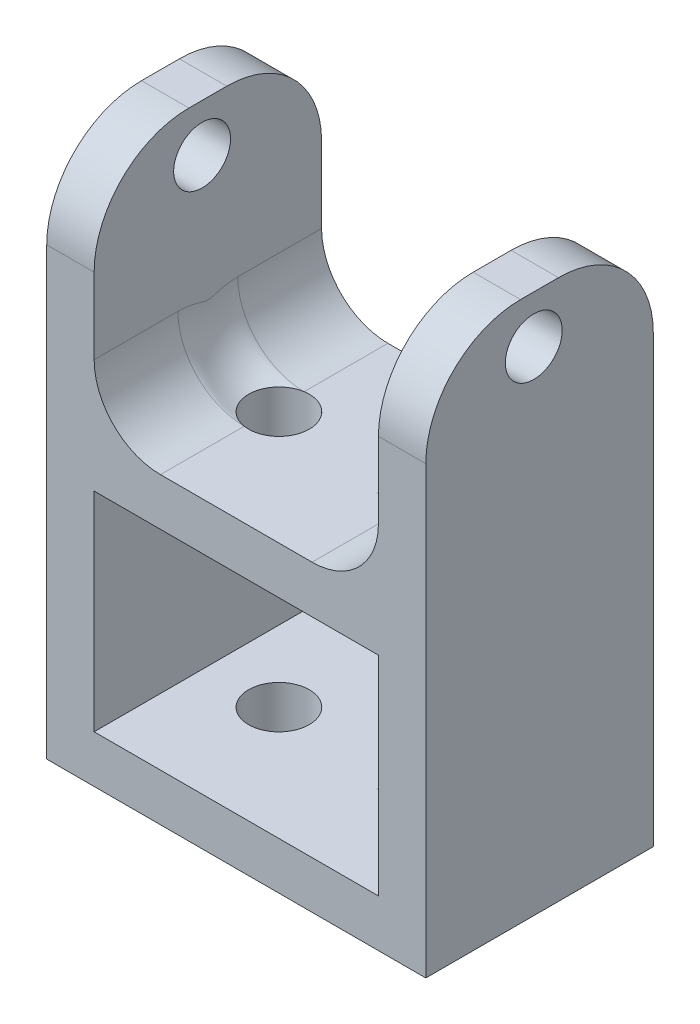
SolidWorks part; units mm, degrees
note: The reader was unsure of these and kept them because the rebuilt part matched: shared geometry of "Sketch1<5>".
material "ABS"
ref_plane "Front Plane" through (0, 0, 0) normal (0, 0, 1) x (1, 0, 0)
ref_plane "Top Plane" through (0, 0, 0) normal (0, 1, 0) x (1, 0, 0)
ref_plane "Right Plane" through (0, 0, 0) normal (1, 0, 0) x (0, 0, -1)
sketch "Sketch1" plane through (0, 0, 0) normal (0, 1, 0) x (1, 0, 0)
  line L0 (15, -12) -> (-15, 12) construction
  line L1 (15, 12) -> (-15, -12) construction
  line L7 (-15, 12) -> (15, 12)
  line L8 (-15, 12) -> (-15, -12)
  line L9 (-15, -12) -> (15, -12)
  line L10 (15, 12) -> (15, -12)
  point P6 (0, 0)
  dimension "D3" = 24
  dimension "D4" = 30
extrude "Base-superior" add sketch "Sketch1" along normal blind 5
sketch "Esboço2" plane through (0, 0, 0) normal (1, 0, 0) x (0, 0, -1)
  line L0 (12, 5) -> (-12, 5) construction
  line L1 (-12, 30) -> (12, 30)
  line L2 (-12, 30) -> (-12, -27)
  line L3 (-12, -27) -> (12, -27)
  line L4 (12, 30) -> (12, -27)
  line L5 (12, 5) -> (12, 0) construction
  line L6 (12, 0) -> (-12, 0) construction
  line L7 (-12, 5) -> (-12, 0) construction
  dimension "D1" = 27
  dimension "D2" = 25
extrude "Placa-lateral" add sketch "Esboço2" along normal blind 5 from vertex at 15 starting at point (15, 5, 12)
extrude "Base-inferior" add sketch "Sketch1<5>" along normal blind 5 from vertex
sketch "Sketch1<5>" plane through (0, 0, 0) normal (0, 1, 0) x (1, 0, 0) same geometry as "Sketch1"
sketch "Sketch7" plane through (0, 0, 0) normal (0, -1, 0) x (1, 0, 0)
  circle A0 centre (-7.5, 0) radius 3.2
  circle A1 centre (7.5, 0) radius 3.2
  dimension "D1" = 6.4
  dimension "D2" = 6.4
  dimension "D4" = 15
  dimension "D5" = 7.5
extrude "Furo-Parafuso" cut sketch "Sketch7" against normal through all both and the other way through all
sketch "Esboço3" plane through (20, 0, 0) normal (1, 0, 0) x (0, 0, -1)
  line L0 (12, -27) -> (12, 30) construction
  line L1 (12, 30) -> (-12, 30) construction
  line L2 (-8, 30) -> (8, 30)
  line L3 (171.9642, 12.9971) -> (0.7947, 38.0125) construction
  line L4 (171.9642, 12.9971) -> (3.1989, -24.9907) construction
  line L5 (171.9642, 12.9971) -> (1.4421, -16.1061) construction
  line L6 (171.9642, 12.9971) -> (0.1526, -7.1418) construction
  line L7 (171.9642, 12.9971) -> (-0.6659, 1.8777) construction
  line L8 (171.9642, 12.9971) -> (-1.0112, 10.9277) construction
  line L9 (171.9642, 12.9971) -> (-0.8825, 19.9834) construction
  line L10 (171.9642, 12.9971) -> (-0.28, 29.0199) construction
  arc A0 (-8, 30) -> (-4.3806, -26.7362) centre (171.9642, 12.9971) ccw
  arc A1 (12, -26.8126) -> (8, 30) centre (171.9642, 12.9971) cw
  arc A2 (-8, 30) -> (-6.8958, 39.1753) centre (171.9642, 12.9971) cw
  arc A3 (8, 30) -> (8.8585, 36.8695) centre (171.9642, 12.9971) cw
  arc A4 (12, -26.8126) -> (11.1522, -23.2364) centre (171.9642, 12.9971) ccw
  circle A5 centre (0.7947, 38.0125) radius 3
  arc A6 (-6.8958, 39.1753) -> (8.8585, 36.8695) centre (0.9813, 38.0224) cw
  arc A7 (11.1522, -23.2364) -> (-4.3806, -26.7362) centre (3.3858, -24.9863) cw
  arc A8 (5.1357, -32.7527) -> (2.1343, 45.8996) centre (171.9642, 12.9971) cw construction
  circle A9 centre (3.1989, -24.9907) radius 3
  circle A10 centre (1.4421, -16.1061) radius 3
  circle A11 centre (0.1526, -7.1418) radius 3
  circle A12 centre (-0.6659, 1.8777) radius 3
  circle A13 centre (-1.0112, 10.9277) radius 3
  circle A14 centre (-0.8825, 19.9834) radius 3
  circle A15 centre (-0.28, 29.0199) radius 3
  dimension "D4" = 6
  dimension "D6" = 6
  dimension "D14" = 6
  dimension "D15" = 6
  dimension "D16" = 6
  dimension "D17" = 6
  dimension "D18" = 6
  dimension "D19" = 6
  dimension "D3" = 4
  dimension "D1" = 4
  dimension "D5" = 8
  dimension "D7" = 8
  dimension "D8" = 3
  dimension "D9" = 6
  dimension "D2" = 9
  dimension "D10" = 12
  dimension "D11" = 15
  dimension "D12" = 18
  dimension "D13" = 21
fillet "Filete-interno" radius 7 1 edges at (15, 5, 0)
sketch "Furo-vareta" plane through (0, 0, 0) normal (1, 0, 0) x (0, 0, -1)
  circle A0 centre (-0.6067, 25) radius 3
  arc A1 (2.1343, 45.8996) -> (5.1357, -32.7527) centre (171.9642, 12.9971) ccw construction
  dimension "D1" = 6
  dimension "D2" = 20
extrude "Furo-Vareta8mm" cut sketch "Furo-vareta" against normal through all both and the other way through all
fillet "Filete1" radius 10 2 edges at (17.5, 30, -12) (17.5, 30, 12)
mirror "Espelhar-Peça-Central" about plane through (0, 0, 0) normal (1, 0, 0) of bodies 120
equation "\"D1@Sketch7\"=\"D2@Sketch7\""
equation "\"D14@Esboço3\"=\"D6@Esboço3\""
equation "\"D15@Esboço3\"=\"D6@Esboço3\""
equation "\"D16@Esboço3\"=\"D6@Esboço3\""
equation "\"D17@Esboço3\"=\"D6@Esboço3\""
equation "\"D18@Esboço3\"=\"D6@Esboço3\""
equation "\"D19@Esboço3\"=\"D6@Esboço3\""
equation "\"D4@Esboço3\"=\"D6@Esboço3\""
